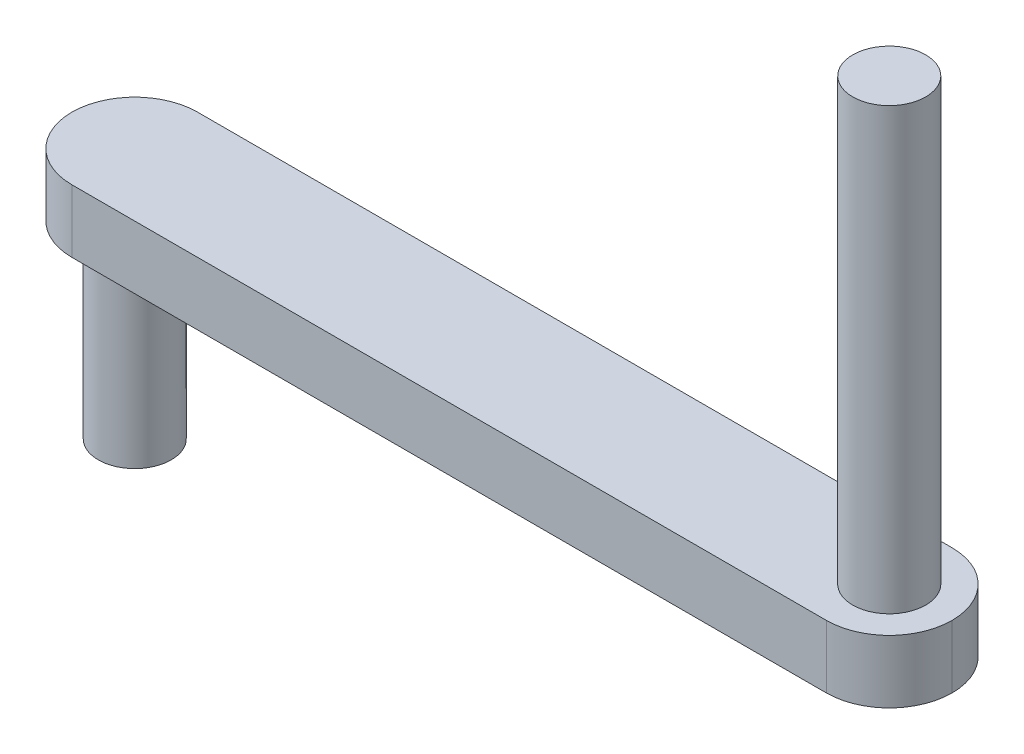
SolidWorks part; units mm, degrees
ref_plane "Front Plane" through (0, 0, 0) normal (0, 0, 1) x (1, 0, 0)
ref_plane "Top Plane" through (0, 0, 0) normal (0, 1, 0) x (1, 0, 0)
ref_plane "Right Plane" through (0, 0, 0) normal (1, 0, 0) x (0, 0, -1)
sketch "Sketch1" plane through (0, 0, 0) normal (0, 1, 0) x (1, 0, 0)
  line L1 (0, 0) -> (70, 0)
  line L2 (0, 0) -> (0, 10)
  line L3 (0, 10) -> (70, 10)
  line L4 (70, 0) -> (70, 10)
  dimension "D1" = 10
  dimension "D2" = 70
extrude "Boss-Extrude1" add sketch "Sketch1" along normal blind 5
fillet "Fillet1" radius 5 4 edges at (70, 2.5, -10) (70, 2.5, 0) (0, 2.5, -10) (0, 2.5, 0)
sketch "Sketch2" plane through (0, 0, 0) normal (0, -1, 0) x (1, 0, 0)
  circle A0 centre (5, -5) radius 2.9
extrude "Boss-Extrude2" add sketch "Sketch2" along normal blind 15
sketch "Sketch3" plane through (0, 5, 0) normal (0, 1, 0) x (1, 0, 0)
  circle A0 centre (65, 5) radius 2.9
extrude "Boss-Extrude3" add sketch "Sketch3" along normal blind 35
